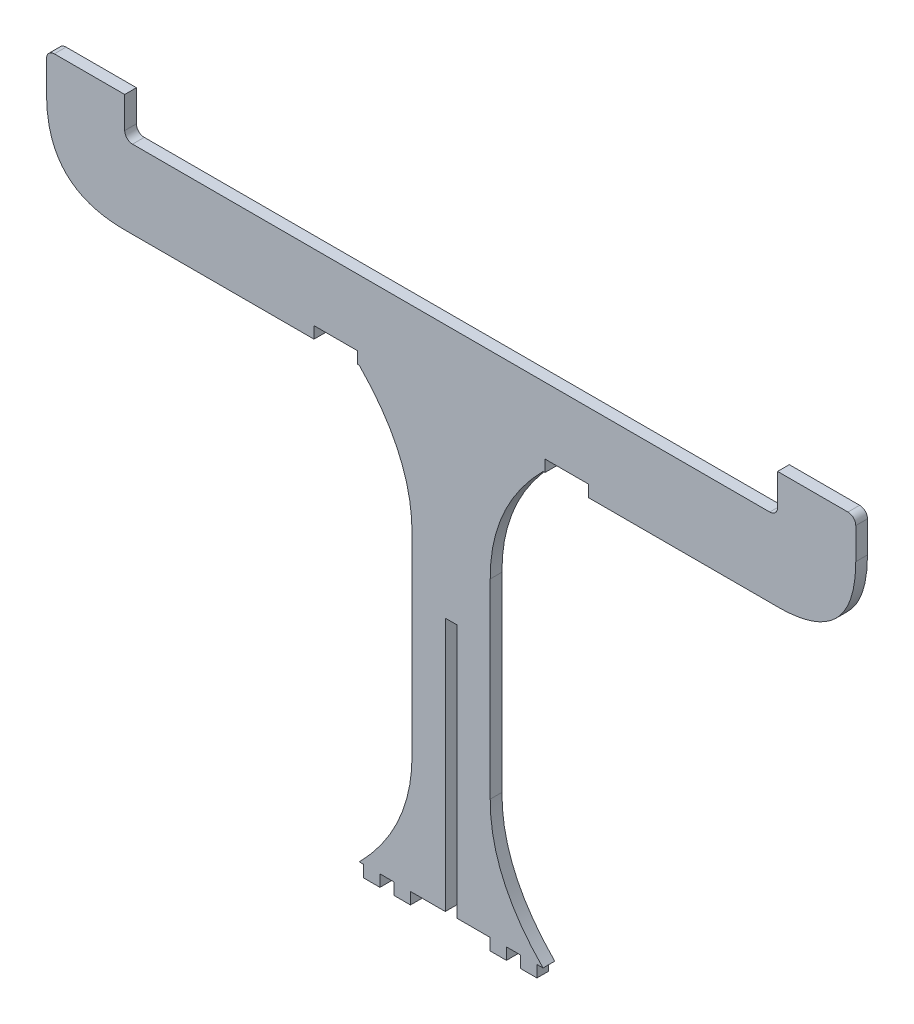
SolidWorks part; units mm, degrees
ref_plane "Přední rovina" through (0, 0, 0) normal (0, 0, 1) x (1, 0, 0)
ref_plane "Horní rovina" through (0, 0, 0) normal (0, 1, 0) x (1, 0, 0)
ref_plane "Pravá rovina" through (0, 0, 0) normal (1, 0, 0) x (0, 0, -1)
sketch "Skica1" plane through (0, 0, 0) normal (0, 0, 1) x (1, 0, 0)
  line L0 (-30.6426, 2.6943) -> (16.3574, 2.6943)
  line L1 (-7.1426, 2.6943) -> (-7.1426, -107.3057)
  line L2 (16.3574, -107.3057) -> (-30.6426, -107.3057)
  line L3 (-17.1426, 9.0001) -> (-17.1426, -176.0586) construction
  line L4 (27.2473, -27.3057) -> (-64.2445, -27.3057) construction
  line L5 (15.3668, -77.3057) -> (-64.2445, -77.3057) construction
  line L6 (-17.1426, -27.8784) -> (-17.1426, -76.656)
  line L7 (2.8574, -27.8784) -> (2.8574, -76.656)
  line L24 (-7.1426, -15.139) -> (-7.1426, 72.526) construction
  line L25 (10.652, -107.3057) -> (10.652, -110.3057)
  line L26 (10.652, -107.3057) -> (14.802, -107.3057)
  line L27 (14.802, -107.3057) -> (14.802, -110.3057)
  line L28 (10.652, -110.3057) -> (14.802, -110.3057)
  line L29 (2.852, -107.3057) -> (2.852, -110.3057)
  line L30 (2.852, -107.3057) -> (7.002, -107.3057)
  line L31 (7.002, -107.3057) -> (7.002, -110.3057)
  line L32 (2.852, -110.3057) -> (7.002, -110.3057)
  line L33 (-25.348, -110.3057) -> (-29.498, -110.3057)
  line L34 (-29.498, -107.3057) -> (-29.498, -110.3057)
  line L35 (-25.348, -107.3057) -> (-29.498, -107.3057)
  line L36 (-25.348, -107.3057) -> (-25.348, -110.3057)
  line L37 (-17.548, -110.3057) -> (-21.698, -110.3057)
  line L38 (-21.698, -107.3057) -> (-21.698, -110.3057)
  line L39 (-17.548, -107.3057) -> (-21.698, -107.3057)
  line L40 (-17.548, -107.3057) -> (-17.548, -110.3057)
  line L41 (-190.6426, 2.6943) -> (100.2644, 2.6943) construction
  line L42 (16.3574, 2.6943) -> (16.3574, 73.8241) construction
  line L43 (-30.6426, 73.8241) -> (-30.6426, 2.6943) construction
  line L44 (-110.6426, 2.6943) -> (-110.6426, 52.9232) construction
  line L45 (-190.6426, 32.6943) -> (86.9117, 32.6943) construction
  line L46 (-30.6426, 2.6943) -> (-90.6426, 2.6943)
  line L47 (-90.6426, -13.7924) -> (-90.6426, 96.8534) construction
  line L48 (-70.6426, -7.8313) -> (-70.6426, 84.4343) construction
  line L49 (-194.5635, 22.6943) -> (-7.1426, 22.6943) construction
  line L50 (-108.6426, 32.6943) -> (-90.6426, 32.6943)
  line L51 (-90.6426, 32.6943) -> (-90.6426, 24.6943)
  line L52 (-110.6426, 22.6943) -> (-110.6426, 30.6943)
  line L53 (16.3574, 2.6943) -> (76.3574, 2.6943)
  line L54 (-110.6426, 22.6943) -> (-110.6426, 2.6943) construction
  line L55 (76.3574, 32.6943) -> (76.3574, 24.6943)
  line L56 (-110.6426, 2.6943) -> (-90.6426, 2.6943) construction
  line L57 (94.3574, 32.6943) -> (76.3574, 32.6943)
  line L58 (-88.6426, 22.6943) -> (74.3574, 22.6943)
  line L59 (-7.1426, 22.6943) -> (-7.1426, 2.6943)
  line L60 (96.3574, 22.6943) -> (96.3574, 30.6943)
  line L61 (96.3574, 22.6943) -> (96.3574, 2.6943) construction
  line L62 (96.3574, 2.6943) -> (76.3574, 2.6943) construction
  arc A0 (74.3574, 22.6943) -> (76.3574, 24.6943) centre (74.3574, 24.6943) ccw
  arc A1 (-88.6426, 22.6943) -> (-90.6426, 24.6943) centre (-88.6426, 24.6943) cw
  arc A2 (-110.6426, 30.6943) -> (-108.6426, 32.6943) centre (-108.6426, 30.6943) cw
  arc A3 (96.3574, 30.6943) -> (94.3574, 32.6943) centre (94.3574, 30.6943) ccw
  spline S0 degree 2 poles (-30.6426, 2.6943) (-17.0251, -11.1181) (-17.1426, -27.8784) knots 0 0 0 1 1 1
  spline S1 degree 2 poles (-30.6426, -107.3057) (-17.0093, -93.4583) (-17.1426, -76.656) knots 0 0 0 1 1 1
  spline S2 degree 2 poles (16.3574, 2.6943) (2.7399, -11.1181) (2.8574, -27.8784) knots 0 0 0 1 1 1
  spline S3 degree 2 poles (16.3574, -107.3057) (2.724, -93.4583) (2.8574, -76.656) knots 0 0 0 1 1 1
  spline S4 degree 2 poles (-110.6426, 22.6943) (-110.6426, 2.6943) (-90.6426, 2.6943) knots 0 0 0 1 1 1
  spline S5 degree 2 poles (96.3574, 22.6943) (96.3574, 2.6943) (76.3574, 2.6943) knots 0 0 0 1 1 1
  point P37 (-110.6426, 22.6943)
  point P54 (-110.6426, 32.6943)
  point P55 (-90.6426, 32.6943)
  point P56 (-90.6426, 22.6943)
  point P70 (-90.6426, 22.6943)
  point P73 (-110.6426, 32.6943)
  dimension "D15" = 60
  dimension "D17" = 2
  dimension "D18" = 2
  dimension "D1" = 110
  dimension "D2" = 23.5
  dimension "D3" = 30
  dimension "D4" = 30
  dimension "D5" = 30.6498
  dimension "D6" = 23.5
  dimension "D7" = 47
  dimension "D8" = 30
  dimension "D9" = 30
  dimension "D10" = 20
  dimension "D11" = 80
  dimension "D12" = 20
  dimension "D13" = 40
  dimension "D14" = 10
extrude "Přidat vysunutím2" add sketch "Skica1" along normal blind 3 contours S1 L2 L1 L0 S0 L6 | L2 S3 L7 S2 L0 L1 | L0 | L0 | L0 | L0 | L40 L2 L38 L37 | L36 L2 L34 L33 | L29 L32 L31 L2 | L25 L28 L27 L2 region at (-61.2298, 14.2338, 0) region at (-13.8581, -52.3107, 0) region at (46.9445, 14.2338, 0) region at (-0.4272, -52.3107, 0) region at (4.927, -108.8057, 0) region at (-19.623, -108.8057, 0) region at (-27.423, -108.8057, 0) region at (12.727, -108.8057, 0)
sketch "Skica2" plane through (0, 0, 0) normal (0, 0, -1) x (-1, 0, 0)
  line L0 (7.1426, -122.7143) -> (7.1426, 122.7143) construction
  line L1 (-2.8574, -27.8784) -> (-2.8574, -76.656) construction
  line L2 (17.1426, -27.8784) -> (17.1426, -76.656) construction
  line L3 (-2.852, -107.3057) -> (17.548, -107.3057) construction
  line L4 (8.6426, -42.3057) -> (5.6426, -42.3057)
  line L5 (8.6426, -42.3057) -> (8.6426, -107.3057)
  line L6 (8.6426, -107.3057) -> (5.6426, -107.3057)
  line L7 (5.6426, -42.3057) -> (5.6426, -107.3057)
  line L8 (8.6426, -42.3057) -> (5.6426, -107.3057) construction
  line L9 (8.6426, -107.3057) -> (5.6426, -42.3057) construction
  line L10 (54.5828, 0) -> (-40.2975, 0) construction
  line L11 (-27.9374, -5.6943) -> (-16.8574, 5.6943) construction
  line L12 (42.2226, 5.6943) -> (31.1426, 5.6943)
  line L13 (42.2226, 5.6943) -> (42.2226, -5.6943)
  line L14 (42.2226, -5.6943) -> (31.1426, -5.6943)
  line L15 (31.1426, 5.6943) -> (31.1426, -5.6943)
  line L16 (42.2226, 5.6943) -> (31.1426, -5.6943) construction
  line L17 (42.2226, -5.6943) -> (31.1426, 5.6943) construction
  line L18 (-27.9374, 5.6943) -> (-16.8574, -5.6943) construction
  line L19 (-27.9374, -5.6943) -> (-16.8574, -5.6943)
  line L20 (-16.8574, 5.6943) -> (-16.8574, -5.6943)
  line L21 (-27.9374, 5.6943) -> (-16.8574, 5.6943)
  line L22 (-27.9374, 5.6943) -> (-27.9374, -5.6943)
  point P6 (7.1426, -74.8057)
  point P13 (7.1426, 0)
  point P14 (36.6826, 0)
  point P22 (32.7238, 3.6539)
  point P24 (-22.3974, 0)
  dimension "D1" = 10
  dimension "D2" = 10
  dimension "D3" = 65
  dimension "D4" = 3
  dimension "D5" = 24
  dimension "D6" = 3
  dimension "D7" = 11.08
extrude "Odebrat vysunutím1" cut sketch "Skica2" against normal blind 3
